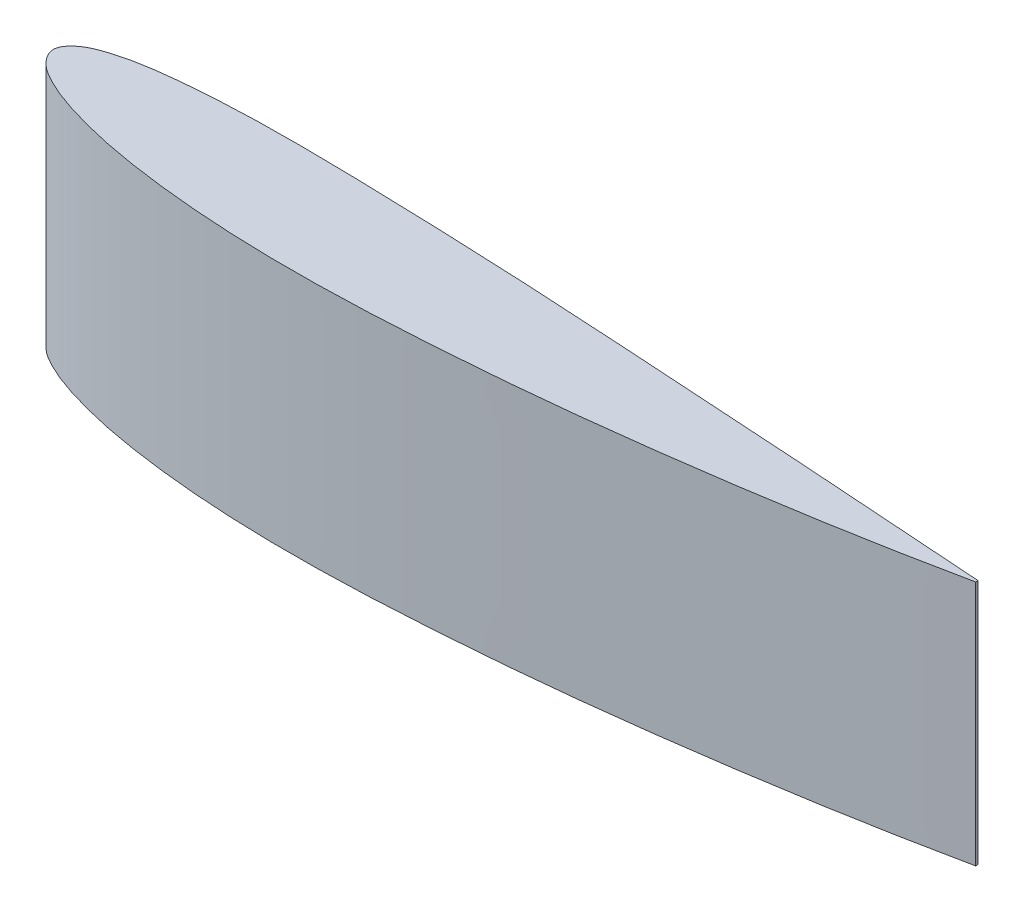
SolidWorks part; units mm, degrees
ref_plane "Front Plane" through (0, 0, 0) normal (0, 0, 1) x (1, 0, 0)
ref_plane "Top Plane" through (0, 0, 0) normal (0, 1, 0) x (1, 0, 0)
ref_plane "Right Plane" through (0, 0, 0) normal (1, 0, 0) x (0, 0, -1)
curve "Curve1"
  spline degree 3 poles (1, 0.0013, 0) (0.9833, 0.0047, 0) (0.9501, 0.0115, 0) (0.8835, 0.024, 0) (0.8002, 0.0379, 0) (0.7002, 0.0522, 0) (0.6002, 0.0641, 0) (0.5001, 0.0729, 0) (0.4001, 0.0788, 0) (0.3166, 0.0798, 0) (0.2499, 0.077, 0) (0.1999, 0.073, 0) (0.1498, 0.0666, 0) (0.108, 0.0587, 0) (0.0748, 0.0498, 0) (0.0496, 0.0416, 0) (0.0282, 0.0322, 0) (0.0098, 0.0207, 0) (-0.0063, 0.0009, 0) (0.0104, -0.0165, 0) (0.0285, -0.0245, 0) (0.0497, -0.0305, 0) (0.0749, -0.0348, 0) (0.1083, -0.0385, 0) (0.1499, -0.0414, 0) (0.2, -0.0425, 0) (0.25, -0.0424, 0) (0.3167, -0.0409, 0) (0.4, -0.0382, 0) (0.5, -0.0336, 0) (0.6, -0.0276, 0) (0.7, -0.0214, 0) (0.8, -0.0151, 0) (0.8833, -0.0093, 0) (0.95, -0.0048, 0) (0.9833, -0.0025, 0) (1, -0.0013, 0) knots 0 0 0 0 0.025012 0.049959 0.099673 0.149206 0.198581 0.247805 0.296917 0.345953 0.370492 0.395091 0.419815 0.444799 0.45749 0.470406 0.483879 0.491264 0.503459 0.513609 0.520451 0.533235 0.545691 0.558032 0.582609 0.607135 0.631652 0.656174 0.705234 0.75432 0.803437 0.852566 0.901701 0.950849 0.975423 1 1 1 1
sketch "Sketch1" plane through (0, 0, 0) normal (0, 0, 1) x (1, 0, 0)
  line L0 (-30.2439, 0) -> (269.7561, 0) construction
  line L1 (269.7561, 0.39) -> (269.7561, -0.39)
  spline S1 degree 3 poles (269.7561, 0.39) (264.7588, 1.414) (254.7775, 3.4593) (234.7977, 7.2056) (209.8095, 11.3564) (179.8038, 15.6525) (149.8031, 19.2352) (119.7893, 21.8586) (89.7824, 23.6351) (64.7467, 23.9358) (44.7379, 23.1075) (29.719, 21.8937) (14.6812, 19.9716) (2.166, 17.6048) (-7.8114, 14.927) (-15.3757, 12.4925) (-21.7845, 9.6559) (-27.3126, 6.2169) (-32.1334, 0.2696) (-27.1259, -4.9579) (-21.7011, -7.3422) (-15.3205, -9.1532) (-7.7812, -10.4518) (2.2361, -11.56) (14.7402, -12.4129) (29.7543, -12.7549) (44.7577, -12.7072) (64.7596, -12.2657) (89.7642, -11.4712) (119.7661, -10.0886) (149.7593, -8.2916) (179.7575, -6.4237) (209.7609, -4.5329) (234.7555, -2.7916) (254.7573, -1.4485) (264.7563, -0.7428) (269.7561, -0.39) knots 0 0 0 0 0.025012 0.049959 0.099673 0.149206 0.198581 0.247805 0.296917 0.345953 0.370492 0.395091 0.419815 0.444799 0.45749 0.470406 0.483879 0.491264 0.503459 0.513609 0.520451 0.533235 0.545691 0.558032 0.582609 0.607135 0.631652 0.656174 0.705234 0.75432 0.803437 0.852566 0.901701 0.950849 0.975423 1 1 1 1
  point P3 (44.7561, 5)
  point P7 (0, 0)
  point P8 (0, 0)
  point P11 (194.7561, 0)
  dimension "D3" = 75
  dimension "D2" = 5
  dimension "D5" = 75
extrude "Boss-Extrude1" add sketch "Sketch1" along normal blind 80
move or copy body "Body-Move/Copy2" bodies to move or copy 101 copy no rotation origin (0, 0, 0) rotation axis (1, 0, 0) rotation angle 90
